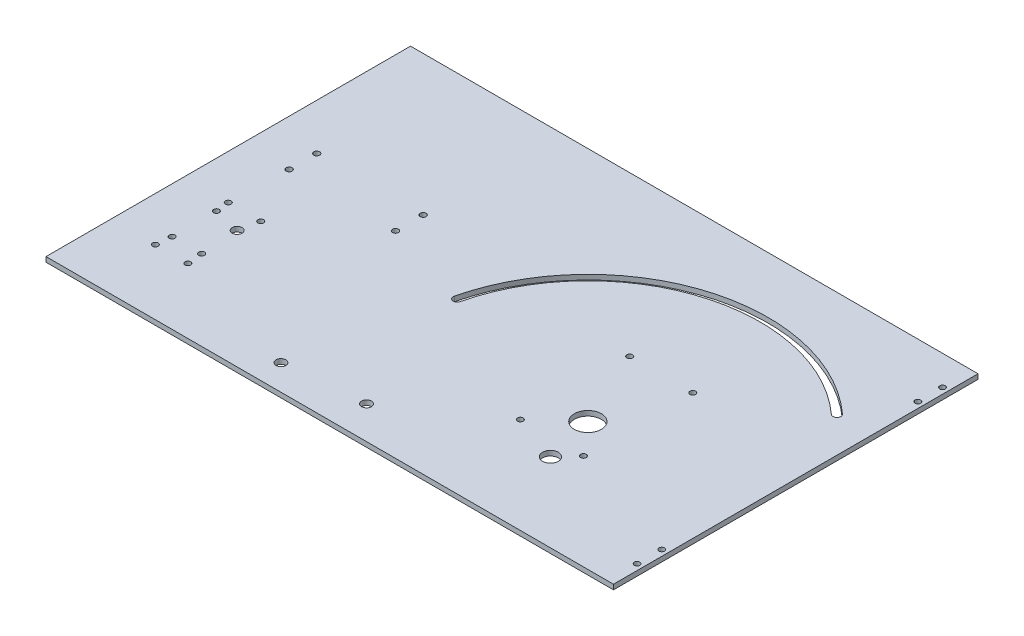
SolidWorks part; units mm, degrees
ref_plane "Front Plane" through (0, 0, 0) normal (0, 0, 1) x (1, 0, 0)
ref_plane "Top Plane" through (0, 0, 0) normal (0, 1, 0) x (1, 0, 0)
ref_plane "Right Plane" through (0, 0, 0) normal (1, 0, 0) x (0, 0, -1)
sketch "Sketch1" plane through (0, 0, 0) normal (0, 1, 0) x (1, 0, 0)
  line L1 (-158.75, 88.9) -> (158.75, 88.9)
  line L2 (-158.75, 88.9) -> (-158.75, -88.9)
  line L3 (-158.75, -88.9) -> (158.75, -88.9)
  line L4 (158.75, 88.9) -> (158.75, -88.9)
  line L5 (-158.75, 88.9) -> (158.75, -88.9) construction
  line L6 (-158.75, -88.9) -> (158.75, 88.9) construction
  circle A0 centre (-111.76, -12.7) radius 3.175
  circle A1 centre (107.95, -6.35) radius 8.7313
  circle A4 centre (-129.032, 55.88) radius 1.905
  circle A5 centre (-60.452, 55.88) radius 1.905
  circle A7 centre (-129.032, 38.1) radius 1.905
  circle A8 centre (-60.452, 38.1) radius 1.905
  point P0 (0, 0)
  dimension "D3" = 6.35
  dimension "D4" = 17.4625
  dimension "D14" = 3.81
  dimension "D17" = 17.78
  dimension "D1" = 317.5
  dimension "D2" = 177.8
  dimension "D5" = 46.99
  dimension "D6" = 266.7
  dimension "D7" = 95.25
  dimension "D8" = 76.2
  dimension "D13" = 29.718
  dimension "D15" = 68.58
  dimension "D16" = 127
extrude "Boss-Extrude1" add sketch "Sketch1" along normal blind 3.175
sketch "Sketch2" plane through (0, 3.175, 0) normal (0, 1, 0) x (1, 0, 0)
  line L0 (-158.75, 88.9) -> (-158.75, -88.9) construction
  line L1 (-158.75, -88.9) -> (158.75, -88.9) construction
  circle A0 centre (-89.0817, -33.177) radius 1.905
  circle A1 centre (-132.1376, -36.4483) radius 1.905
  dimension "D1" = 3.81
  dimension "D2" = 69.6683
  dimension "D3" = 52.4517
  dimension "D4" = 55.723
  dimension "D5" = 43.18
extrude "Cut-Extrude1" [suppressed] cut sketch "Sketch2" against normal through all
sketch "Sketch3" plane through (0, 0, 0) normal (0, -1, 0) x (-1, 0, 0)
  line L0 (158.75, -88.9) -> (-158.75, -88.9) construction
  line L1 (158.75, 88.9) -> (158.75, -88.9) construction
  circle A0 centre (23.8295, -72.39) radius 3.175
  circle A1 centre (-26.7643, -67.818) radius 3.175
  dimension "D1" = 6.35
  dimension "D2" = 4.572
  dimension "D3" = 16.51
  dimension "D4" = 185.5143
  dimension "D5" = 50.8
extrude "Cut-Extrude2" cut sketch "Sketch3" against normal through all
sketch "Sketch4" plane through (0, 3.175, 0) normal (0, 1, 0) x (1, 0, 0)
  line L0 (-158.75, -88.9) -> (158.75, -88.9) construction
  line L1 (158.75, 88.9) -> (133.35, 88.9)
  line L2 (158.75, 88.9) -> (158.75, -88.9)
  line L3 (158.75, -88.9) -> (133.35, -88.9)
  line L4 (133.35, 88.9) -> (133.35, -88.9)
  dimension "D1" = 25.4
extrude "Cut-Extrude3" cut sketch "Sketch4" against normal through all
sketch "Sketch5" plane through (0, 3.175, 0) normal (0, 1, 0) x (1, 0, 0)
  line L0 (133.35, 88.9) -> (-158.75, 88.9) construction
  line L1 (133.35, 88.9) -> (133.35, -88.9) construction
  circle A0 centre (115.57, -38.1) radius 5.08
  dimension "D3" = 10.16
  dimension "D1" = 127
  dimension "D2" = 17.78
extrude "Cut-Extrude4" cut sketch "Sketch5" against normal through all
sketch "Sketch7" plane through (0, 3.175, 0) normal (0, 1, 0) x (1, 0, 0)
  line L0 (133.35, 88.9) -> (133.35, -88.9) construction
  line L1 (133.35, 88.9) -> (-158.75, 88.9) construction
  line L2 (-158.75, 88.9) -> (-158.75, -88.9) construction
  line L3 (-158.75, -88.9) -> (133.35, -88.9) construction
  circle A1 centre (125.73, 43.4975) radius 1.8415
  circle A2 centre (85.09, 43.4975) radius 1.8415
  circle A3 centre (85.09, -26.9875) radius 1.8415
  circle A4 centre (125.73, -26.9875) radius 1.8415
  circle A5 centre (-130.175, -46.99) radius 1.8415
  circle A6 centre (-109.22, -46.99) radius 1.8415
  circle A7 centre (-129.2225, -37.1475) radius 1.8415
  circle A8 centre (-110.1725, -37.1475) radius 1.8415
  circle A9 centre (-129.2225, -8.5725) radius 1.8415
  circle A10 centre (-130.175, 0) radius 1.8415
  circle A11 centre (-109.22, 0) radius 1.8415
  dimension "D1" = 7.62
  dimension "D5" = 3.683
  dimension "D10" = 3.683
  dimension "D15" = 3.683
  dimension "D2" = 40.64
  dimension "D3" = 70.485
  dimension "D4" = 61.9125
  dimension "D6" = 28.575
  dimension "D7" = 20.955
  dimension "D8" = 0.9525
  dimension "D9" = 19.05
  dimension "D11" = 88.9
  dimension "D12" = 8.5725
  dimension "D13" = 28.575
  dimension "D14" = 9.8425
extrude "Cut-Extrude6" cut sketch "Sketch7" against normal through all
sketch "Sketch8" plane through (0, 0, 0) normal (0, -1, 0) x (1, 0, 0)
  line L1 (-158.75, -88.9) -> (-158.75, 88.9) construction
  line L2 (-158.75, 88.9) -> (133.35, 88.9) construction
  line L3 (133.35, 88.9) -> (133.35, -88.9)
  line L4 (133.35, -88.9) -> (-158.75, -88.9) construction
  line L5 (133.35, -88.9) -> (-158.75, -88.9)
  line L6 (-158.75, -88.9) -> (-158.75, -146.05)
  line L7 (-158.75, -146.05) -> (209.55, -146.05)
  line L8 (209.55, -146.05) -> (209.55, 88.9)
  line L9 (209.55, 88.9) -> (133.35, 88.9)
  line L12 (133.35, -88.9) -> (133.35, 88.9) construction
  dimension "D1" = 76.2
  dimension "D2" = 57.15
extrude "Boss-Extrude2" add sketch "Sketch8" against normal through all
sketch "Sketch9" plane through (0, 0, 0) normal (0, -1, 0) x (1, 0, 0)
  line L2 (209.55, -146.05) -> (209.55, 88.9) construction
  arc A0 (185.8528, -79.875) -> (182.4472, -76.1056) centre (184.15, -77.9903) ccw
  arc A1 (-0.15, -19.402) -> (-5.0917, -20.5792) centre (-2.6208, -19.9906) ccw
  circle A2 centre (107.95, 6.35) radius 113.665 construction
  arc A3 (182.4472, -76.1056) -> (-0.15, -19.402) centre (107.95, 6.35) cw
  arc A4 (185.8528, -79.875) -> (-5.0917, -20.5792) centre (107.95, 6.35) cw
  arc A5 (-5.0917, -20.5792) -> (-2.0046, -22.4547) centre (-2.6208, -19.9906) ccw construction
  arc A6 (-2.0046, -22.4547) -> (-0.15, -19.402) centre (-2.6208, -19.9906) ccw construction
  arc A7 (182.2464, -79.672) -> (185.8528, -79.875) centre (184.15, -77.9903) ccw construction
  arc A8 (182.4472, -76.1056) -> (182.2464, -79.672) centre (184.15, -77.9903) ccw construction
  circle A12 centre (107.95, 6.35) radius 8.7313 construction
  dimension "D1" = 5.08
  dimension "D6" = 227.33
  dimension "D2" = 25.4
  dimension "D5" = 186.7708
extrude "Cut-Extrude7" cut sketch "Sketch9" against normal through all
sketch "Sketch10" plane through (0, 0, 0) normal (0, -1, 0) x (1, 0, 0)
  line L0 (209.55, -146.05) -> (209.55, 88.9) construction
  line L1 (-158.75, 88.9) -> (209.55, 88.9) construction
  line L2 (209.55, -28.575) -> (142.4229, -28.575) construction
  line L3 (-158.75, -146.05) -> (209.55, -146.05) construction
  line L4 (209.55, 88.9) -> (207.01, 88.9)
  line L5 (209.55, 88.9) -> (209.55, -146.05)
  line L6 (209.55, -146.05) -> (207.01, -146.05)
  line L7 (207.01, 88.9) -> (207.01, -146.05)
  circle A0 centre (203.2, 69.85) radius 1.8034
  circle A1 centre (203.2, 53.975) radius 1.8034
  circle A2 centre (203.2, -111.125) radius 1.8034
  circle A3 centre (203.2, -127) radius 1.8034
  dimension "D2" = 3.6068
  dimension "D1" = 15.875
  dimension "D3" = 6.35
  dimension "D4" = 19.05
  dimension "D5" = 2.54
extrude "Cut-Extrude8" cut sketch "Sketch10" against normal through all
